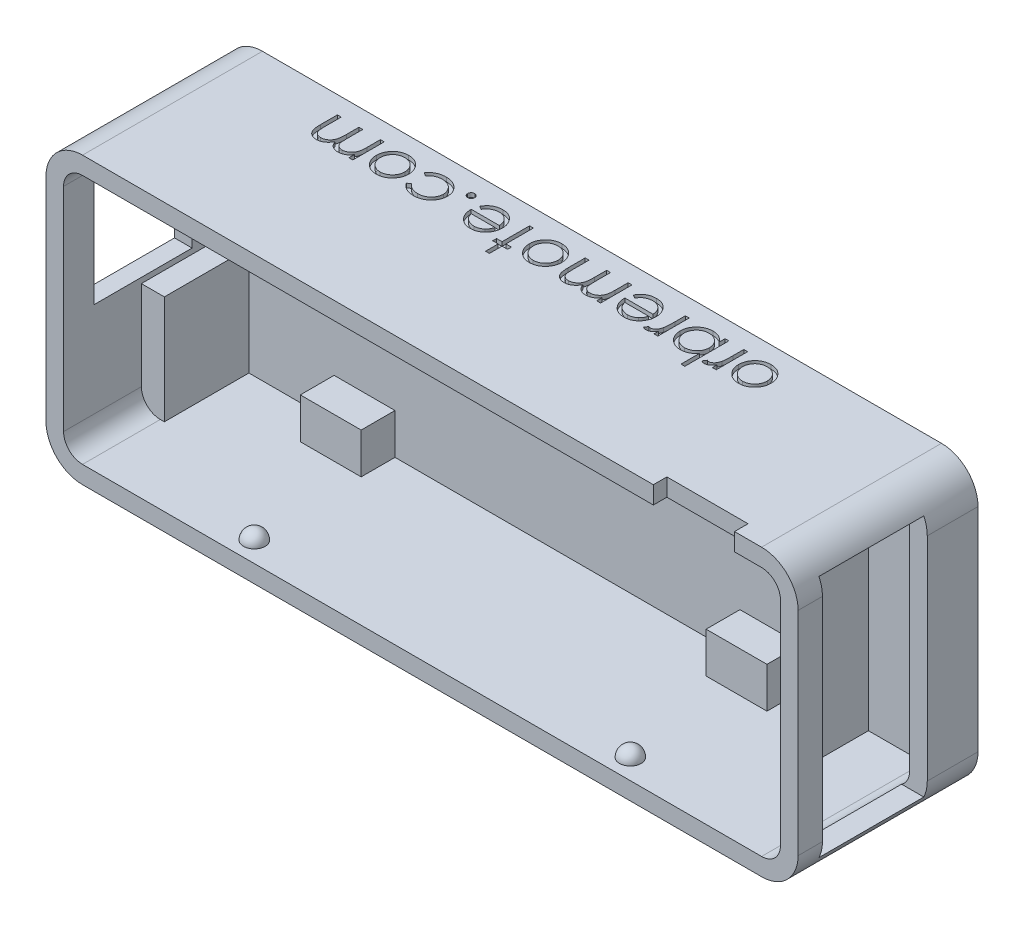
SolidWorks part; units mm, degrees
material "PLA"
ref_plane "Front Plane" through (0, 0, 0) normal (0, 0, 1) x (1, 0, 0)
ref_plane "Top Plane" through (0, 0, 0) normal (0, 1, 0) x (1, 0, 0)
ref_plane "Right Plane" through (0, 0, 0) normal (1, 0, 0) x (0, 0, -1)
sketch "Sketch2" plane through (0, 0, 0) normal (0, 0, 1) x (1, 0, 0)
  line L1 (2.4, -43.153) -> (-47.8, -43.153)
  line L2 (3.8, -44.553) -> (3.8, -60.253)
  line L3 (2.4, -61.653) -> (-47.8, -61.653)
  line L4 (-49.2, -44.553) -> (-49.2, -60.253)
  arc A0 (3.8, -44.553) -> (2.4, -43.153) centre (2.4, -44.553) ccw
  arc A1 (2.4, -61.653) -> (3.8, -60.253) centre (2.4, -60.253) ccw
  arc A2 (-49.2, -60.253) -> (-47.8, -61.653) centre (-47.8, -60.253) ccw
  arc A3 (-49.2, -44.553) -> (-47.8, -43.153) centre (-47.8, -44.553) cw
  point P2 (3.8, -43.153)
  point P9 (-49.2, -61.653)
  point P14 (-49.2, -43.153)
  dimension "D1" = 18.5
  dimension "D3" = 1.4
  dimension "D2" = 53
extrude "Boss-Extrude1" add sketch "Sketch2" along normal blind 12 contours L2 A1 L3 A2 L4 A3 L1 A0
shell "Shell1" thickness 1.3 removed face at (-22.7, -52.403, 12) outward yes
sketch "Sketch3" plane through (0, -61.653, 0) normal (0, 1, 0) x (1, 0, 0)
  line L0 (-9.6, -10.5) -> (-8, -10.5)
  line L1 (2.4, -12) -> (-47.8, -12) construction
  line L2 (5.1, -12) -> (5.1, 1.3) construction
  arc A0 (-8, -10.5) -> (-9.6, -10.5) centre (-8.8, -10.5) ccw
  dimension "D4" = 0.8
  dimension "D1" = 1.5
  dimension "D2" = 13.9
  dimension "D3" = 1.6
revolve "Revolve1" add sketch "Sketch3" angle 360 about L0
ref_plane "Plane1" through (0, -52.403, 0) normal (0, 1, 0) x (1, 0, 0)
mirror "Mirror1" about plane through (0, -52.403, 0) normal (0, 1, 0) of "Revolve1"
sketch "Sketch9" plane through (0, 0, 0) normal (0, 0, 1) x (1, 0, 0)
  line L0 (-47.5, -61.653) -> (-47.5, -53.653)
  line L1 (2.4, -61.653) -> (-47.8, -61.653) construction
  line L2 (2.4, -43.153) -> (-47.8, -43.153) construction
  line L3 (-49.2, -44.553) -> (-49.2, -60.253) construction
  line L4 (-47.5, -53.653) -> (-49.2, -53.653)
  line L8 (2.4, -43.153) -> (-47.8, -43.153)
  line L9 (-49.2, -44.553) -> (-49.2, -60.253)
  line L10 (-47.8, -61.653) -> (2.4, -61.653)
  line L11 (3.8, -60.253) -> (3.8, -44.553)
  line L12 (-47.2, -43.153) -> (-47.8, -43.153)
  line L13 (-49.2, -44.553) -> (-49.2, -60.253)
  line L14 (-47.8, -61.653) -> (-47.5, -61.653)
  arc A4 (3.8, -44.553) -> (2.4, -43.153) centre (2.4, -44.553) ccw
  arc A5 (-47.8, -43.153) -> (-49.2, -44.553) centre (-47.8, -44.553) ccw
  arc A6 (-49.2, -60.253) -> (-47.8, -61.653) centre (-47.8, -60.253) ccw
  arc A7 (2.4, -61.653) -> (3.8, -60.253) centre (2.4, -60.253) ccw
  arc A9 (-47.8, -43.153) -> (-49.2, -44.553) centre (-47.8, -44.553) ccw
  arc A10 (-49.2, -60.253) -> (-47.8, -61.653) centre (-47.8, -60.253) ccw
  line M4 (-49.2, -44.553) -> (-49.2, -60.253)
  arc M5 (-49.2, -60.253) -> (-47.8, -61.653) centre (-47.8, -60.253) ccw
  line M6 (-47.8, -61.653) -> (2.4, -61.653)
  dimension "D1" = 1.7
  dimension "D3" = 8
  dimension "D2" = 0
extrude "Boss-Extrude3" add sketch "Sketch9" along normal blind 6.25 contours L0 L4 M4 M5 M6 region at (-48.3329, -57.5354, 0)
sketch "Sketch10" plane through (5.1, 0, 0) normal (1, 0, 0) x (0, 0, -1)
  line L0 (6.6, -52.403) -> (-6.6, -52.403) construction
  line L1 (-2.45, -61.403) -> (-10.2, -61.403)
  line L2 (-2.45, -61.403) -> (-2.45, -43.403)
  line L3 (-2.45, -43.403) -> (-10.2, -43.403)
  line L4 (-10.2, -61.403) -> (-10.2, -43.403)
  line L5 (-2.45, -61.403) -> (-10.2, -43.403) construction
  line L6 (-2.45, -43.403) -> (-10.2, -61.403) construction
  line L7 (1.3, -44.553) -> (1.3, -60.253) construction
  point P0 (-6.325, -52.403)
  dimension "D1" = 0
  dimension "D2" = 3.75
  dimension "D3" = 18
  dimension "D4" = 7.75
extrude "Cut-Extrude1" cut sketch "Sketch10" against normal blind 2.7
sketch "Sketch11" plane through (0, 0, 0) normal (0, 0, 1) x (1, 0, 0)
  line L0 (6.6, -52.403) -> (-6.6, -52.403) construction
  line L1 (-1.7, -61.653) -> (-3.7, -61.653)
  line L2 (-1.7, -61.653) -> (-1.7, -43.153)
  line L3 (-1.7, -43.153) -> (-3.7, -43.153)
  line L4 (-3.7, -61.653) -> (-3.7, -43.153)
  line L5 (-1.7, -61.653) -> (-3.7, -43.153) construction
  line L6 (-1.7, -43.153) -> (-3.7, -61.653) construction
  line L8 (-50.5, -44.553) -> (-50.5, -60.253) construction
  point P0 (-2.7, -52.403)
  dimension "D1" = 0
  dimension "D2" = 47.8
  dimension "D3" = 2
  dimension "D4" = 18.5
extrude "Boss-Extrude4" add sketch "Sketch11" along normal blind 4
ref_plane "Plane2" through (-22.7, 0, 0) normal (-1, 0, 0) x (0, 0, 1)
mirror "Mirror3" about plane through (-22.7, 0, 0) normal (-1, 0, 0) of "Revolve1", "Mirror1"
sketch "Sketch12" plane through (0, 0, 0) normal (0, 0, 1) x (1, 0, 0)
  line L0 (-3.7, -61.653) -> (-47.5, -61.653) construction
  line L1 (-6.7, -61.653) -> (-11.2, -61.653)
  line L2 (-6.7, -61.653) -> (-6.7, -58.653)
  line L3 (-6.7, -58.653) -> (-11.2, -58.653)
  line L4 (-11.2, -61.653) -> (-11.2, -58.653)
  line L5 (-3.7, -43.153) -> (-3.7, -61.653) construction
  dimension "D1" = 3
  dimension "D2" = 4.5
  dimension "D3" = 3
extrude "Boss-Extrude5" add sketch "Sketch12" along normal blind 2.5
pattern_linear "LPattern1" count 2 spacing 30 along (-1, 0, 0) count 2 spacing 15.5 along (0, 1, 0) of "Boss-Extrude5"
sketch "Sketch19" plane through (0, -41.853, 0) normal (0, 1, 0) x (1, 0, 0)
  line L0 (-7.4973, 0) -> (-45.0839, 0) construction
  text T0 "orbremote.com"
extrude "Cut-Extrude4" cut sketch "Sketch19" against normal blind 0.3
sketch "Sketch21" plane through (0, -62.953, 0) normal (0, -1, 0) x (1, 0, 0)
  line L0 (-45.043, 0) -> (0, 0) construction
  text T0 "OrB Remote Inspection Services" font "Century Gothic" height in points 8
extrude "Cut-Extrude5" cut sketch "Sketch21" against normal blind 0.3
sketch "Sketch22" plane through (0, 0, -1.3) normal (0, 0, -1) x (-1, 0, 0)
  line L1 (3.7, -43.153) -> (3.7, -61.653) construction
  circle A0 centre (11.7, -51.9812) radius 1.75
  dimension "D2" = 3.5
  dimension "D1" = 8
extrude "Cut-Extrude6" [suppressed] cut sketch "Sketch22" against normal blind 1.3
pattern_linear "LPattern2" [suppressed] count 4 spacing 10 of bodies 114
sketch "Sketch23" plane through (-50.5, 0, 0) normal (-1, 0, 0) x (0, 0, 1)
  line L0 (12, -44.553) -> (12, -60.253) construction
  line L2 (12, -61.653) -> (6.25, -61.653) construction
  circle A0 centre (5.5, -52.403) radius 1.75
  dimension "D3" = 3.5
  dimension "D1" = 6.5
  dimension "D2" = 9.25
extrude "Cut-Extrude7" [suppressed] cut sketch "Sketch23" against normal blind 1.3
sketch "Sketch24" plane through (0, -41.853, 0) normal (0, 1, 0) x (1, 0, 0)
  line L0 (2.4, -12) -> (2.4, 1.3) construction
  line L1 (2.4, -12) -> (-47.8, -12) construction
  circle A0 centre (-7.6, -6) radius 1.25
  dimension "D1" = 2.5
  dimension "D2" = 10
  dimension "D3" = 6
extrude "Cut-Extrude8" [suppressed] cut sketch "Sketch24" against normal blind 1.3
pattern_linear "LPattern3" [suppressed] count 4 spacing 10 count 2 spacing 19.8 of bodies 117
sketch "Sketch25" plane through (0, -41.853, 0) normal (0, 1, 0) x (1, 0, 0)
  line L0 (2.4, -12) -> (-47.8, -12) construction
  line L1 (0.4, -12) -> (-5.6, -12)
  line L2 (0.4, -12) -> (0.4, -11)
  line L3 (0.4, -11) -> (-5.6, -11)
  line L4 (-5.6, -12) -> (-5.6, -11)
  line L5 (2.4, -12) -> (2.4, 1.3) construction
  dimension "D1" = 2
  dimension "D2" = 1
  dimension "D3" = 6
extrude "Cut-Extrude9" cut sketch "Sketch25" against normal blind 10
mirror "Mirror2" [suppressed] about plane through (0, -52.403, 0) normal (0, 1, 0)
sketch "Sketch26" plane through (-50.5, 0, 0) normal (-1, 0, 0) x (0, 0, 1)
  line L0 (-1.3, -44.553) -> (-1.3, -60.253) construction
  line L1 (9.75, -53.253) -> (2.5, -53.253)
  line L2 (9.75, -53.253) -> (9.75, -43.253)
  line L3 (9.75, -43.253) -> (2.5, -43.253)
  line L4 (2.5, -53.253) -> (2.5, -43.253)
  line L5 (12, -41.853) -> (-1.3, -41.853) construction
  dimension "D1" = 10
  dimension "D2" = 3.8
  dimension "D3" = 7.25
  dimension "D4" = 1.4
extrude "Cut-Extrude10" cut sketch "Sketch26" against normal blind 4
equation "\"D1@Boss-Extrude1\" = \"BoxDepth\"'depth"
equation "\"D1@Shell1\"=\"WallThickness\""
equation "\"BoxWidth\"= 18.5mm'inner width"
equation "\"D1@Sketch2\"=\"BoxWidth\""
equation "\"BoxLength\"= 53mm'inner length"
equation "\"D2@Sketch2\"=\"BoxLength\""
equation "\"D3@Sketch2\" = \"CornerRadius\"'inner corner radius"
equation "\"CornerRadius\"= 1.4mm'inner corner radius"
equation "\"BoxDepth\"= 12mm'inner depth"
equation "\"WallThickness\"= 1.3mm"
equation "\"LatchOffEdge\"= 1.5mm"
equation "\"LatchRadius\"= 0.8mm"
equation "\"D2@Sketch3\"=(\"BoxLength\"+\"WallThickness\"*2)/4"
equation "\"D1@Sketch3\"=\"LatchOffEdge\""
equation "\"D3@Sketch3\"=\"LatchRadius\"*2"
equation "\"D4@Sketch3\"=\"LatchRadius\""
equation "\"PortWidth\"= 18mm"
equation "\"PortHeight\"= 7.75mm"
equation "\"PortOffsetBottom\"= 3.75mm"
equation "\"D3@Sketch10\"=\"PortWidth\""
equation "\"D2@Sketch10\"=\"PortOffsetBottom\""
equation "\"D4@Sketch10\"=\"PortHeight\""
equation "\"D1@Cut-Extrude1\"=\"WallThickness\"+\"CornerRadius\""
equation "\"D4@Sketch11\"=\"BoxWidth\""
equation "\"D4@LPattern1\"=\"BoxWidth\"-\"D1@Sketch12\""
equation "\"D1@Cut-Extrude6\"=\"WallThickness\""
equation "\"D2@Sketch23\"=\"BoxWidth\"/2"
equation "\"D1@Cut-Extrude7\"=\"WallThickness\""
equation "\"D1@Cut-Extrude8\"=\"WallThickness\""
equation "\"D4@LPattern3\"=\"BoxWidth\"+\"WallThickness\""
